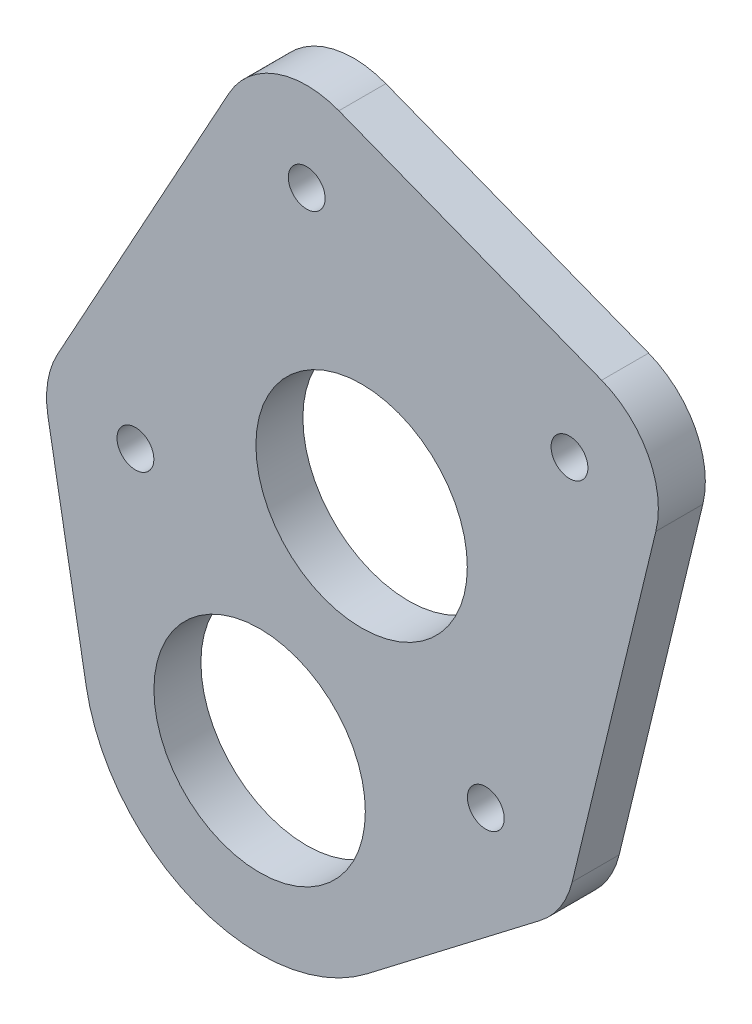
SolidWorks part; units mm, degrees
material "6061-T6 (SS)"
ref_plane "Front Plane" through (0, 0, 0) normal (0, 0, 1) x (1, 0, 0)
ref_plane "Top Plane" through (0, 0, 0) normal (0, 1, 0) x (1, 0, 0)
ref_plane "Right Plane" through (0, 0, 0) normal (1, 0, 0) x (0, 0, -1)
sketch "Sketch1" plane through (0, 0, 0) normal (0, 0, 1) x (1, 0, 0)
  line L0 (13.7841, 35.5191) -> (0, 0) construction
  line L1 (-16.7874, 26.949) -> (30.5715, 8.5702) construction
  line L2 (13.7841, 35.5191) -> (24.1222, 62.1585) construction
  line L3 (0, 0) -> (23.1556, 0) construction
  line L4 (-28.6152, 24.8409) -> (-23.4431, -4.1783)
  line L5 (14.4876, -18.8982) -> (37.881, -0.9646)
  line L8 (6.3626, 69.0505) -> (41.8817, 55.2664) construction
  line L9 (-27.315, 32.7377) -> (-4.1651, 74.8393)
  line L10 (42.248, 5.742) -> (53.5583, 52.4383)
  line L11 (10.7092, 80.2509) -> (46.2283, 66.4668)
  circle A0 centre (0, 0) radius 14.2875
  circle A1 centre (13.7841, 35.5191) radius 14.2875
  circle A2 centre (-16.7874, 26.949) radius 2.4892
  circle A3 centre (30.5715, 8.5702) radius 2.4892
  arc A5 (-23.4431, -4.1783) -> (14.4876, -18.8982) centre (0, 0) ccw
  circle A9 centre (0, 0) radius 23.8125 construction
  circle A10 centre (41.8817, 55.2664) radius 2.4892
  circle A11 centre (6.3626, 69.0505) radius 2.4892
  arc A12 (-27.315, 32.7377) -> (-28.6152, 24.8409) centre (-16.7874, 26.949) ccw
  arc A13 (37.881, -0.9646) -> (42.248, 5.742) centre (30.5715, 8.5702) ccw
  arc A14 (53.5583, 52.4383) -> (46.2283, 66.4668) centre (41.8817, 55.2664) ccw
  arc A15 (10.7092, 80.2509) -> (-4.1651, 74.8393) centre (6.3626, 69.0505) ccw
  circle A16 centre (-16.7874, 26.949) radius 12.0142 construction
  circle A17 centre (30.5715, 8.5702) radius 12.0142 construction
  circle A18 centre (41.8817, 55.2664) radius 12.0142 construction
  circle A19 centre (6.3626, 69.0505) radius 12.0142 construction
  point P11 (6.892, 17.7596)
  point P12 (6.892, 17.7596)
  point P17 (24.1222, 62.1585)
  dimension "D1" = 28.575
  dimension "D3" = 4.9784
  dimension "D2" = 38.1
  dimension "D4" = 28.575
  dimension "D5" = 50.8
  dimension "D6" = 68.79
  dimension "D8" = 38.1
  dimension "D7" = 9.525
  dimension "D9" = 9.525
extrude "Boss-Extrude1" add sketch "Sketch1" along normal mid plane 6.35
equation "\"D2@Sketch1\"=60/40"
